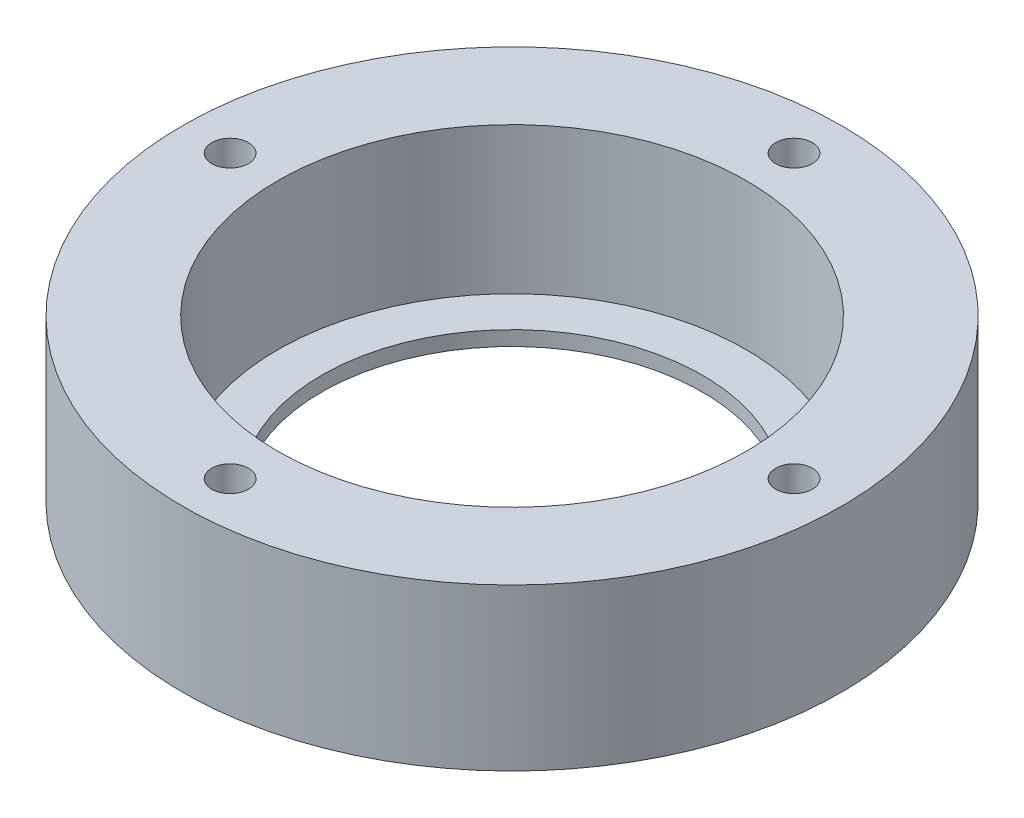
SolidWorks part; units mm, degrees
material "Сплав 2024"
ref_plane "Спереди" through (0, 0, 0) normal (0, 0, 1) x (1, 0, 0)
ref_plane "Сверху" through (0, 0, 0) normal (0, 1, 0) x (1, 0, 0)
ref_plane "Справа" through (0, 0, 0) normal (1, 0, 0) x (0, 0, -1)
sketch "Эскиз1" plane through (0, 0, 0) normal (0, 1, 0) x (1, 0, 0)
  circle A0 centre (0, 0) radius 22.5
  dimension "D1" = 45
extrude "Бобышка-Вытянуть1" add sketch "Эскиз1" along normal blind 11
sketch "Эскиз2" plane through (0, 11, 0) normal (0, 1, 0) x (1, 0, 0)
  circle A0 centre (0, 0) radius 16
  dimension "D1" = 32
extrude "Вырез-Вытянуть1" cut sketch "Эскиз2" against normal blind 10
sketch "Эскиз3" plane through (0, 1, 0) normal (0, 1, 0) x (1, 0, 0)
  circle A0 centre (0, 0) radius 13
  dimension "D1" = 26
extrude "Вырез-Вытянуть2" cut sketch "Эскиз3" against normal through all
sketch "Эскиз4" plane through (0, 11, 0) normal (0, 1, 0) x (1, 0, 0)
  line L0 (0, 25.6262) -> (0, -25.6262) construction
  line L1 (-26.9212, 0) -> (26.9212, 0) construction
  circle A0 centre (0, 0) radius 19.25 construction
  dimension "D1" = 38.5
hole_wizard "Отверстие обработанное метчиком M3x0.51" positions "Эскиз6" profile "Эскиз5" tap size "M3x0.5" standard "Ansi Metric"
sketch "Эскиз6" plane through (0, 11, 0) normal (0, 1, 0) x (1, 0, 0)
  line L0 (-26.9212, 0) -> (26.9212, 0) construction
  line L1 (0, 25.6262) -> (0, -25.6262) construction
  circle A0 centre (0, 0) radius 19.25 construction
  point P0 (-19.25, 0)
  point P6 (0, -19.25)
  point P10 (19.25, 0)
  point P12 (0, 19.25)
sketch "Эскиз5" plane through (-19.25, 11, 0) normal (1, 0, 0) x (0, 0, 1)
  line L0 (0, 0) -> (0, 9.2511)
  line L1 (0, 9.2511) -> (1.25, 8.5)
  line L2 (1.25, 8.5) -> (1.25, 0)
  line L5 (1.25, 0) -> (0, 0)
  line L10 (0, 9.2511) -> (-1.25, 8.5) construction
  line L11 (0, -6.35) -> (0, 107.95) construction
  dimension "Диаметр сверла" = 2.5
  dimension "Глубина сверла" = 8.5
  dimension "Угол заточки сверла" = 118
